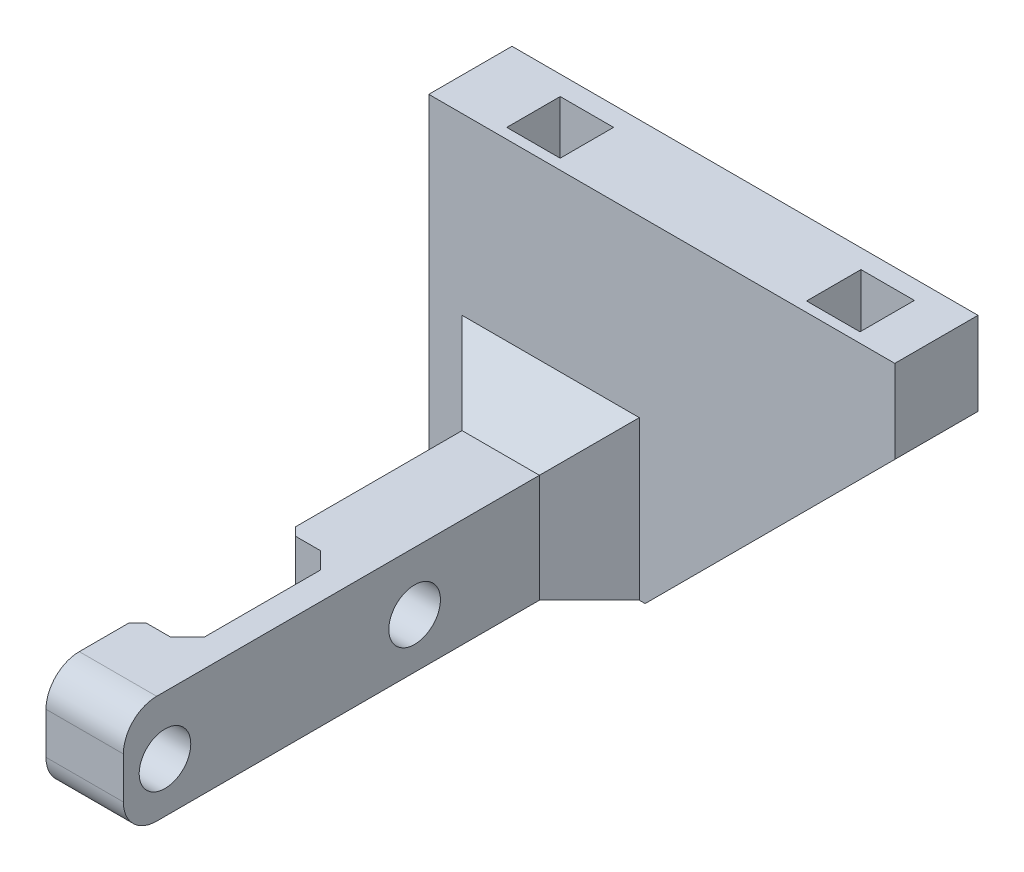
SolidWorks part; units mm, degrees
ref_plane "Front Plane" through (0, 0, 0) normal (0, 0, 1) x (1, 0, 0)
ref_plane "Top Plane" through (0, 0, 0) normal (0, 1, 0) x (1, 0, 0)
ref_plane "Right Plane" through (0, 0, 0) normal (1, 0, 0) x (0, 0, -1)
sketch "Sketch1" plane through (0, 0, 0) normal (0, 1, 0) x (1, 0, 0)
  line L1 (0, 0) -> (28, 0)
  line L2 (0, 0) -> (0, 5)
  line L3 (0, 5) -> (28, 5)
  line L4 (28, 0) -> (28, 5)
  dimension "D1" = 5
  dimension "D2" = 28
extrude "Boss-Extrude1" add sketch "Sketch1" along normal blind 20
chamfer "Chamfer1" distance 15 angle 45 1 edges at (28, 0, -2.5)
sketch "Sketch2" plane through (0, 0, 0) normal (0, 0, 1) x (1, 0, 0)
  line L0 (5, 18) -> (5, 2) construction
  line L1 (5, 18) -> (5, 2)
  line L2 (0, 0) -> (13, 0) construction
  line L3 (5, 6.5) -> (9.6488, 6.5)
  line L4 (5, 6.5) -> (5, 0)
  line L5 (5, 0) -> (9.6488, 0)
  line L6 (9.6488, 6.5) -> (9.6488, 0)
  line M5 (0, 0) -> (13, 0)
  dimension "D1" = 6.5
extrude "Boss-Extrude2" add sketch "Sketch2" along normal blind 28 contours L6 L3 L1 L4 M5 region at (7.3244, 3.25, 0)
sketch "Sketch3" plane through (0, 0, 0) normal (0, -1, 0) x (1, 0, 0)
  line L0 (5, 28) -> (5, 0) construction
  line L1 (5, 22.5) -> (8, 22.5)
  line L2 (5, 22.5) -> (5, 13.5)
  line L3 (5, 13.5) -> (8, 13.5)
  line L4 (8, 22.5) -> (8, 13.5)
  dimension "D1" = 3
  dimension "D2" = 1
  dimension "D3" = 1
extrude "Cut-Extrude1" cut sketch "Sketch3" against normal blind 12.8
chamfer "Chamfer2" distance 1 angle 45 2 edges at (8, 3.25, 13.5) (8, 3.25, 22.5)
fillet "Fillet1" radius 2 2 edges at (7.3244, 6.5, 28) (7.3244, 0, 28)
chamfer "Chamfer3" distance 0.5 angle 45 2 edges at (5, 3.25, 22.5) (5, 3.25, 13.5)
sketch "Sketch4" plane through (5, 0, 0) normal (-1, 0, 0) x (0, 0, 1)
  arc A0 (25.5, 1.45) -> (25.5, 4.55) centre (25.5, 3) ccw construction
  arc A1 (25.5, 4.55) -> (25.5, 1.45) centre (25.5, 3) ccw construction
  arc A2 (10.5, 4.55) -> (10.5, 1.45) centre (10.5, 3) ccw construction
  arc A3 (10.5, 1.45) -> (10.5, 4.55) centre (10.5, 3) ccw construction
  arc A4 (25.5, 1.45) -> (25.5, 4.55) centre (25.5, 3) ccw
  arc A5 (25.5, 4.55) -> (25.5, 1.45) centre (25.5, 3) ccw
  arc A6 (10.5, 4.55) -> (10.5, 1.45) centre (10.5, 3) ccw
  arc A7 (10.5, 1.45) -> (10.5, 4.55) centre (10.5, 3) ccw
extrude "Cut-Extrude2" cut sketch "Sketch4" against normal blind 12.8
chamfer "Chamfer4" distance 3 angle 45 2 edges at (5, 3.25, 0) (9.6488, 3.25, 0)
chamfer "Chamfer5" distance 3 angle 45 1 edges at (7.3244, 6.5, 0)
sketch "Sketch8" plane through (0, 20, 0) normal (0, 1, 0) x (1, 0, 0)
  line L0 (22.254, 1.284) -> (22.254, 1.158) construction
  line L1 (22.254, 0.746) -> (22.254, 1.158) construction
  line L2 (22.254, 3.714) -> (22.254, 1.284) construction
  line L3 (22.254, 3.714) -> (25.164, 3.714) construction
  line L4 (25.164, 3.714) -> (25.164, 0.75) construction
  line L5 (25.164, 0.746) -> (24.43, 0.746) construction
  line L6 (24.43, 0.746) -> (22.254, 0.746) construction
  line L7 (4.214, 2.802) -> (4.214, 2.092) construction
  line L8 (4.214, 2.092) -> (4.214, 0.772) construction
  line L9 (4.858, 0.772) -> (4.214, 0.772) construction
  line L10 (6.602, 0.772) -> (7.122, 0.772) construction
  line L11 (4.858, 0.772) -> (6.602, 0.772) construction
  line L12 (7.122, 0.772) -> (7.122, 3.484) construction
  line L13 (7.122, 3.682) -> (7.122, 3.484) construction
  line L14 (4.214, 3.682) -> (4.214, 2.802) construction
  line L15 (6.328, 3.682) -> (4.214, 3.682) construction
  line L16 (7.122, 3.682) -> (6.328, 3.682) construction
  line L17 (22.254, 1.284) -> (22.254, 1.158)
  line L18 (22.254, 0.746) -> (22.254, 1.158)
  line L19 (22.254, 3.714) -> (22.254, 1.284)
  line L20 (22.254, 3.714) -> (25.164, 3.714)
  line L21 (25.164, 3.714) -> (25.164, 0.75)
  line L22 (25.164, 0.746) -> (24.43, 0.746)
  line L23 (24.43, 0.746) -> (22.254, 0.746)
  line L24 (4.214, 2.802) -> (4.214, 2.092)
  line L25 (4.214, 2.092) -> (4.214, 0.772)
  line L26 (4.858, 0.772) -> (4.214, 0.772)
  line L27 (6.602, 0.772) -> (7.122, 0.772)
  line L28 (4.858, 0.772) -> (6.602, 0.772)
  line L29 (7.122, 0.772) -> (7.122, 3.484)
  line L30 (7.122, 3.682) -> (7.122, 3.484)
  line L31 (4.214, 3.682) -> (4.214, 2.802)
  line L32 (6.328, 3.682) -> (4.214, 3.682)
  line L33 (7.122, 3.682) -> (6.328, 3.682)
  line L34 (25.252, 3.714) -> (22.254, 3.714) construction
  line L35 (25.164, 0.746) -> (22.254, 0.746)
  line L36 (25.164, 0.746) -> (25.164, 3.714)
  line L37 (25.164, 3.714) -> (22.254, 3.714)
  line L38 (22.254, 0.746) -> (22.254, 3.714)
  line L39 (25.314, 0.596) -> (22.104, 0.596)
  line L40 (25.314, 0.596) -> (25.314, 3.864)
  line L41 (25.314, 3.864) -> (22.104, 3.864)
  line L42 (22.104, 0.596) -> (22.104, 3.864)
  line L44 (4.064, 0.622) -> (7.272, 0.622)
  line L45 (4.064, 0.622) -> (4.064, 3.832)
  line L46 (4.064, 3.832) -> (7.272, 3.832)
  line L47 (7.272, 0.622) -> (7.272, 3.832)
  dimension "D1" = 0.15
  dimension "D2" = 0.15
  dimension "D3" = 0.15
  dimension "D4" = 0.15
  dimension "D5" = 0.15
  dimension "D6" = 0.15
  dimension "D7" = 0.15
  dimension "D8" = 0.15
extrude "Cut-Extrude3" cut sketch "Sketch8" against normal blind 5.4 contours L44 L47 L46 L45 L33 L30 L29 L27 L28 L26 L25 L24 L31 L32 | L30 L33 L32 L31 L24 L25 L26 L28 L27 L29 | L22 L36 L21 L20 L19 L17 L18 L23 | L42 L39 L40 L41 L36 L22 L23 L18 L17 L19 L20 L21 region at (23.709, 20, -2.23) region at (5.668, 20, -2.227) region at (23.709, 20, -0.6418) region at (4.1094, 20, -2.227)
